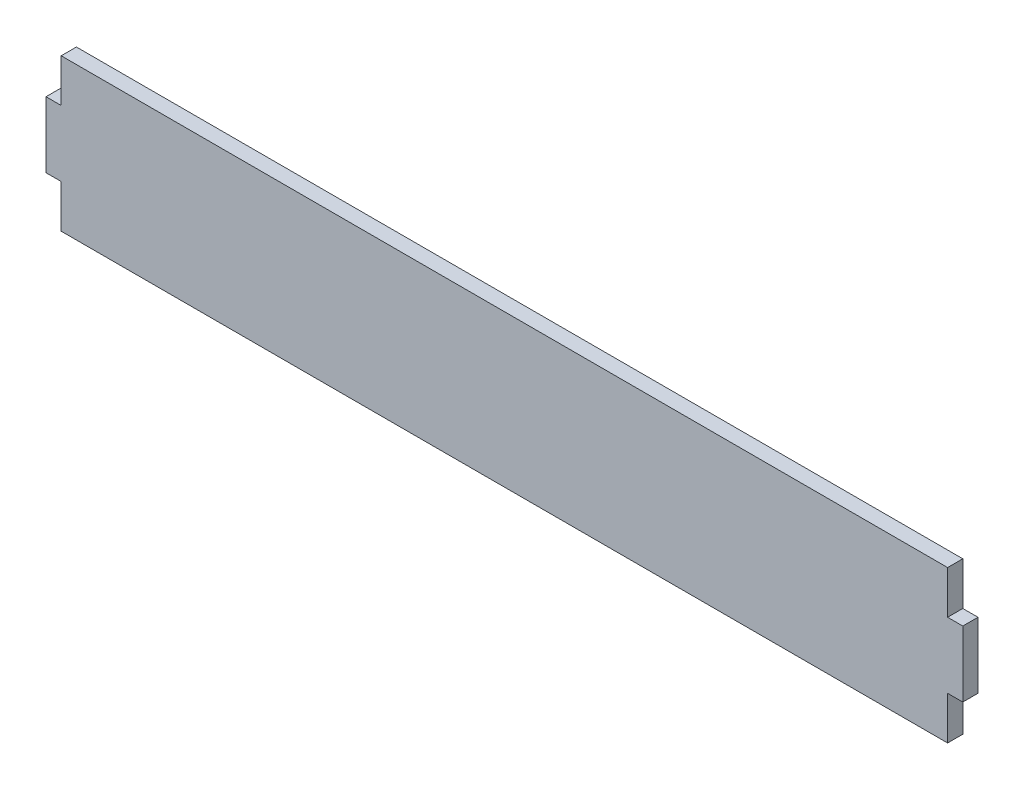
SolidWorks part; units mm, degrees
ref_plane "Front Plane" through (0, 0, 0) normal (0, 0, 1) x (1, 0, 0)
ref_plane "Top Plane" through (0, 0, 0) normal (0, 1, 0) x (1, 0, 0)
ref_plane "Right Plane" through (0, 0, 0) normal (1, 0, 0) x (0, 0, -1)
sketch "Sketch1" plane through (0, 0, 0) normal (0, 0, 1) x (1, 0, 0)
  line L0 (3, 21.5) -> (3, 30)
  line L1 (3, 0) -> (178, 0)
  line L3 (3, 30) -> (178, 30)
  line L5 (0, 21.5) -> (3, 21.5)
  line L6 (0, 21.5) -> (0, 8.5)
  line L7 (0, 8.5) -> (3, 8.5)
  line L10 (0, 0) -> (3, 0) construction
  line L11 (3, 8.5) -> (3, 0)
  line L12 (0, 8.5) -> (0, 0) construction
  line L13 (90.5, 15) -> (90.5, 3.5137) construction
  line L14 (0, 15) -> (181, 15) construction
  line L15 (181, -90.1289) -> (181, 82.7145) construction
  line L16 (178, 8.5) -> (178, 0)
  line L17 (181, 8.5) -> (178, 8.5)
  line L18 (178, 21.5) -> (178, 30)
  line L19 (181, 21.5) -> (178, 21.5)
  line L20 (181, 21.5) -> (181, 8.5)
  dimension "D1" = 30
  dimension "D2" = 13
  dimension "D3" = 3
extrude "Boss-Extrude1" add sketch "Sketch1" along normal blind 3
